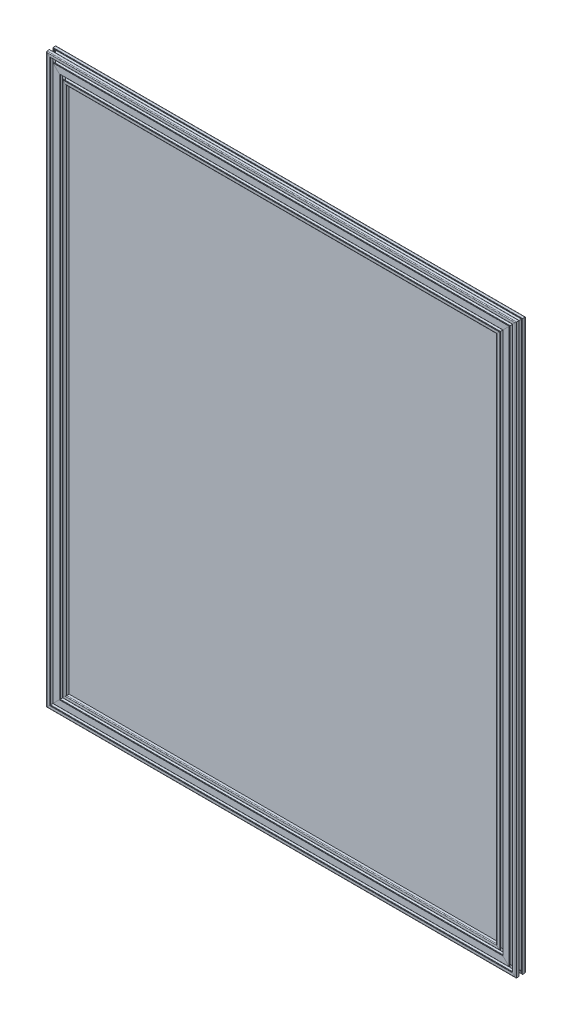
SolidWorks part; units mm, degrees
ref_plane "前视基准面" through (0, 0, 0) normal (0, 0, 1) x (1, 0, 0)
ref_plane "上视基准面" through (0, 0, 0) normal (0, 1, 0) x (1, 0, 0)
ref_plane "右视基准面" through (0, 0, 0) normal (1, 0, 0) x (0, 0, -1)
other "Configuration Table"
sketch "草图1" plane through (0, 0, 0) normal (0, 0, 1) x (1, 0, 0)
  line L1 (-448, 548.25) -> (448, 548.25)
  line L2 (-448, 548.25) -> (-448, -548.25)
  line L3 (-448, -548.25) -> (448, -548.25)
  line L4 (448, 548.25) -> (448, -548.25)
  line L5 (-448, 548.25) -> (448, -548.25) construction
  line L6 (-448, -548.25) -> (448, 548.25) construction
  point P0 (0, 0)
  dimension "D1" = 1096.5
  dimension "D2" = 896
other "铝型材 20 X 40 X R1.5(1)" corner treatment miter
ref_plane "基准面1" through (-448, -548.25, 0) normal (1, 0, 0) x (0, 0, -1)
sketch "Sketch1" plane through (-448, -548.25, 0) normal (1, 0, 0) x (0, 0, -1)
  line L0 (-3.6, 10) -> (-3.6, 9.5)
  line L1 (-3.6, 9.5) -> (-3.1, 9.5)
  line L2 (-3.1, 9.5) -> (-3.1, 8.5)
  line L3 (-3.1, 8.5) -> (-5.5, 8.5)
  line L4 (8.85, -10) -> (2.75, -3.9)
  line L5 (-10, -16.4) -> (-10, -3.6)
  line L6 (8.5, 10) -> (3.6, 10)
  line L7 (10, 8.5) -> (10, 3.6)
  line L8 (0, 14.8756) -> (0, 0) construction
  line L9 (0, 0) -> (10, 0) construction
  line L10 (-5.5, 8.5) -> (-5.5, 6.65)
  line L11 (-5.5, 6.65) -> (-2.75, 3.9)
  line L12 (-2.75, 3.9) -> (2.75, 3.9)
  line L13 (5.5, 6.65) -> (2.75, 3.9)
  line L14 (5.5, 8.5) -> (5.5, 6.65)
  line L15 (3.1, 8.5) -> (5.5, 8.5)
  line L16 (3.1, 9.5) -> (3.1, 8.5)
  line L17 (3.6, 9.5) -> (3.1, 9.5)
  line L18 (3.6, 10) -> (3.6, 9.5)
  line L19 (-3.6, 10) -> (-8.5, 10)
  line L20 (10, 3.6) -> (9.5, 3.6)
  line L21 (9.5, 3.6) -> (9.5, 3.1)
  line L22 (9.5, 3.1) -> (8.5, 3.1)
  line L23 (8.5, 3.1) -> (8.5, 5.5)
  line L24 (8.5, 5.5) -> (6.65, 5.5)
  line L25 (6.65, 5.5) -> (3.9, 2.75)
  line L26 (3.9, 2.75) -> (3.9, -2.75)
  line L27 (6.65, -5.5) -> (3.9, -2.75)
  line L28 (8.5, -5.5) -> (6.65, -5.5)
  line L29 (8.5, -3.1) -> (8.5, -5.5)
  line L30 (9.5, -3.1) -> (8.5, -3.1)
  line L31 (9.5, -3.6) -> (9.5, -3.1)
  line L32 (10, -3.6) -> (9.5, -3.6)
  line L33 (8.85, -10) -> (2.75, -16.1)
  line L34 (-8.85, -10) -> (-2.75, -16.1)
  line L35 (-8.85, -10) -> (-2.75, -3.9)
  line L39 (2.75, -3.9) -> (-2.75, -3.9)
  line L46 (-10, -3.6) -> (-9.5, -3.6)
  line L47 (-9.5, -3.6) -> (-9.5, -3.1)
  line L48 (-9.5, -3.1) -> (-8.5, -3.1)
  line L49 (-8.5, -3.1) -> (-8.5, -5.5)
  line L50 (-8.5, -5.5) -> (-6.65, -5.5)
  line L51 (-6.65, -5.5) -> (-3.9, -2.75)
  line L52 (-3.9, -2.75) -> (-3.9, 2.75)
  line L53 (-6.65, 5.5) -> (-3.9, 2.75)
  line L54 (-8.5, 5.5) -> (-6.65, 5.5)
  line L55 (-8.5, 3.1) -> (-8.5, 5.5)
  line L56 (-9.5, 3.1) -> (-8.5, 3.1)
  line L57 (-9.5, 3.6) -> (-9.5, 3.1)
  line L58 (-10, 3.6) -> (-9.5, 3.6)
  line L60 (-10, 3.6) -> (-10, 8.5)
  line L61 (10, -3.6) -> (10, -16.4)
  line L66 (-8.5, -30) -> (-3.6, -30)
  line L67 (-10, -28.5) -> (-10, -23.6)
  line L72 (-2.75, -16.1) -> (2.75, -16.1)
  line L80 (10, -16.4) -> (9.5, -16.4)
  line L81 (9.5, -16.4) -> (9.5, -16.9)
  line L82 (9.5, -16.9) -> (8.5, -16.9)
  line L83 (8.5, -16.9) -> (8.5, -14.5)
  line L84 (8.5, -14.5) -> (6.65, -14.5)
  line L85 (6.65, -14.5) -> (3.9, -17.25)
  line L86 (3.9, -17.25) -> (3.9, -22.75)
  line L87 (6.65, -25.5) -> (3.9, -22.75)
  line L88 (8.5, -25.5) -> (6.65, -25.5)
  line L89 (8.5, -23.1) -> (8.5, -25.5)
  line L90 (9.5, -23.1) -> (8.5, -23.1)
  line L91 (9.5, -23.6) -> (9.5, -23.1)
  line L92 (10, -23.6) -> (9.5, -23.6)
  line L93 (3.6, -30) -> (3.6, -29.5)
  line L94 (3.6, -29.5) -> (3.1, -29.5)
  line L95 (3.1, -29.5) -> (3.1, -28.5)
  line L96 (3.1, -28.5) -> (5.5, -28.5)
  line L97 (5.5, -28.5) -> (5.5, -26.65)
  line L98 (5.5, -26.65) -> (2.75, -23.9)
  line L99 (2.75, -23.9) -> (-2.75, -23.9)
  line L100 (-5.5, -26.65) -> (-2.75, -23.9)
  line L101 (-5.5, -28.5) -> (-5.5, -26.65)
  line L102 (-3.1, -28.5) -> (-5.5, -28.5)
  line L103 (-3.1, -29.5) -> (-3.1, -28.5)
  line L104 (-3.6, -29.5) -> (-3.1, -29.5)
  line L105 (-3.6, -30) -> (-3.6, -29.5)
  line L106 (-10, -23.6) -> (-9.5, -23.6)
  line L107 (-9.5, -23.6) -> (-9.5, -23.1)
  line L108 (-9.5, -23.1) -> (-8.5, -23.1)
  line L109 (-8.5, -23.1) -> (-8.5, -25.5)
  line L110 (-8.5, -25.5) -> (-6.65, -25.5)
  line L111 (-6.65, -25.5) -> (-3.9, -22.75)
  line L112 (-3.9, -22.75) -> (-3.9, -17.25)
  line L113 (-6.65, -14.5) -> (-3.9, -17.25)
  line L114 (-8.5, -14.5) -> (-6.65, -14.5)
  line L115 (-8.5, -16.9) -> (-8.5, -14.5)
  line L116 (-9.5, -16.9) -> (-8.5, -16.9)
  line L117 (-9.5, -16.4) -> (-9.5, -16.9)
  line L118 (-10, -16.4) -> (-9.5, -16.4)
  line L119 (3.6, -30) -> (8.5, -30)
  line L121 (10, -23.6) -> (10, -28.5)
  line L122 (0, -20) -> (10, -20) construction
  line L125 (3.6, -10) -> (3.6, -9.5)
  line L127 (3.6, -9.5) -> (3.1, -9.5)
  line L129 (3.1, -9.5) -> (3.1, -8.5)
  line L131 (3.1, -8.5) -> (5.5, -8.5)
  line L133 (-3.1, -8.5) -> (-5.5, -8.5)
  line L135 (-3.1, -9.5) -> (-3.1, -8.5)
  line L137 (-3.6, -9.5) -> (-3.1, -9.5)
  line L139 (-3.6, -10) -> (-3.6, -9.5)
  line L141 (-3.6, -10) -> (-3.6, -10.5)
  line L142 (-3.6, -10.5) -> (-3.1, -10.5)
  line L143 (-3.1, -10.5) -> (-3.1, -11.5)
  line L144 (-3.1, -11.5) -> (-5.5, -11.5)
  line L145 (8.5, -10) -> (3.6, -10)
  line L146 (3.1, -11.5) -> (5.5, -11.5)
  line L147 (3.1, -10.5) -> (3.1, -11.5)
  line L148 (3.6, -10.5) -> (3.1, -10.5)
  line L149 (3.6, -10) -> (3.6, -10.5)
  line L150 (-3.6, -10) -> (-8.5, -10)
  line L151 (-10, -16.4) -> (-10, -11.5)
  line L152 (10, -11.5) -> (10, -16.4)
  line L154 (-5.5, -8.5) -> (-5.5, -6.65)
  line L156 (5.5, -8.5) -> (5.5, -6.65)
  line L157 (5.5, -11.5) -> (5.5, -13.35)
  line L158 (-5.5, -11.5) -> (-5.5, -13.35)
  line L160 (-12.2446, -13.3946) -> (-10, -11.15)
  line L161 (13.644, -5.206) -> (10, -8.85)
  line L163 (12.1963, -13.3463) -> (10, -11.15)
  line L164 (-11.1344, -7.7156) -> (-10, -8.85)
  circle A0 centre (0, 0) radius 2.5
  arc A1 (-10, 8.5) -> (-8.5, 10) centre (-8.5, 8.5) cw
  arc A2 (10, 8.5) -> (8.5, 10) centre (8.5, 8.5) ccw
  arc A3 (10, -28.5) -> (8.5, -30) centre (8.5, -28.5) cw
  arc A4 (-10, -28.5) -> (-8.5, -30) centre (-8.5, -28.5) ccw
  circle A5 centre (0, -20) radius 2.5
  arc A12 (-10, -11.5) -> (-8.5, -10) centre (-8.5, -11.5) cw
  arc A13 (10, -11.5) -> (8.5, -10) centre (8.5, -11.5) ccw
  point P0 (-10, 0)
  point P1 (10, 0)
  point P2 (0, 10)
  point P4 (0, 0)
  point P5 (0, -10)
  point P6 (-10, -10)
  point P7 (10, 10)
  point P8 (-10, 10)
  point P12 (-10, -10)
  point P13 (10, -10)
  point P15 (0, -10)
  point P16 (10, -10)
  point P36 (-10, 10)
  point P39 (10, 10)
  point P43 (-10, -20)
  point P44 (10, -20)
  point P62 (0, 0)
  point P88 (0, -30)
  point P89 (0, -20)
  point P90 (-10, -30)
  point P91 (10, -30)
  dimension "D1" = 11
  dimension "D2" = 20
  dimension "D3" = 6.2
  dimension "D4" = 7.2
  dimension "D5" = 6.1
  dimension "D6" = 5
  dimension "D7" = 1.5
  dimension "D8" = 45
  dimension "D14" = 20
  dimension "D15" = 1.5
  dimension "D9" = 0.5
  dimension "D10" = 1
  dimension "D11" = 5.5
  dimension "D12" = 10
  dimension "D13" = 40
  dimension "D16" = 45
  dimension "D17" = 45
  dimension "D18" = 45
  dimension "D19" = 6.2
sketch "草图3" plane through (0, 0, 0) normal (0, 0, 1) x (1, 0, 0)
  line L0 (445.25, -545.5) -> (450.75, -551) construction
  line L1 (-448, 548.25) -> (448, 548.25)
  line L2 (-448, 548.25) -> (-448, -548.25)
  line L3 (-448, -548.25) -> (448, -548.25)
  line L4 (448, 548.25) -> (448, -548.25)
  line L5 (-448, 548.25) -> (448, -548.25) construction
  line L6 (-448, -548.25) -> (448, 548.25) construction
  point P0 (0, 0)
  point P6 (0, 0)
  point P7 (458, -558.25)
base flange "基体-法兰1" sketch "草图3" thickness 3 reverse thickness direction no parameters "D1"=2.5
sketch "折弯-线1" plane through (0, 0, 0) normal (0, 1, 0) x (1, 0, 0)
sketch "边界框1" plane through (0, 0, 0) normal (0, 1, 0) x (1, 0, 0)
sheet metal parameters "钣金10" thickness 3 parameters "D1"=2.5
flat pattern "平板型式10" [suppressed]
sketch "折弯-线2" plane through (0, 0, 0) normal (0, 1, 0) x (1, 0, 0)
sketch "边界框2" [suppressed] plane through (0, 0, 0) normal (0, 1, 0) x (1, 0, 0)
